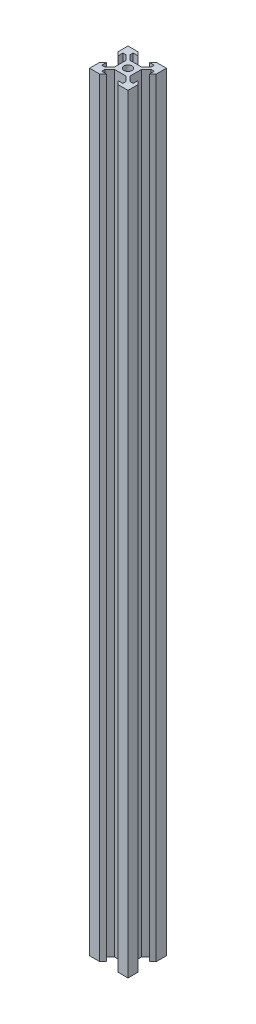
SolidWorks part; units mm, degrees
ref_plane "Front Plane" through (0, 0, 0) normal (0, 0, 1) x (1, 0, 0)
ref_plane "Top Plane" through (0, 0, 0) normal (0, 1, 0) x (1, 0, 0)
ref_plane "Right Plane" through (0, 0, 0) normal (1, 0, 0) x (0, 0, -1)
other "80mm"
sketch "Sketch1" plane through (0, 0, 0) normal (0, 1, 0) x (1, 0, 0)
  line L0 (-4.6984, 10) -> (-3, 8.2)
  line L1 (-10, 10) -> (-4.6984, 10)
  line L2 (-10, 10) -> (-10, 4.9076)
  line L3 (-10, -10) -> (-4.9076, -10)
  line L4 (10, 10) -> (10, 4.6984)
  line L5 (-10, 10) -> (10, -10) construction
  line L6 (-10, -10) -> (10, 10) construction
  line L7 (-3, 8.2) -> (-5.4993, 8.2)
  line L8 (-5.4993, 6.56) -> (-3, 4.0607)
  line L9 (-3, 4.0607) -> (3, 4.0607)
  line L10 (3, 4.0607) -> (5.4993, 6.56)
  line L11 (5.4993, 8.2) -> (3, 8.2)
  line L12 (3, 8.2) -> (4.9076, 10)
  line L13 (4.0607, 3) -> (4.0607, -3)
  line L14 (6.56, 5.4993) -> (4.0607, 3)
  line L15 (8.2, 3) -> (8.2, 5.4993)
  line L16 (10, 4.6984) -> (8.2, 3)
  line L17 (8.2, -3) -> (10, -4.9076)
  line L18 (8.2, -5.4993) -> (8.2, -3)
  line L19 (4.0607, -3) -> (6.56, -5.4993)
  line L20 (3, -4.0607) -> (-3, -4.0607)
  line L21 (5.4993, -6.56) -> (3, -4.0607)
  line L22 (3, -8.2) -> (5.4993, -8.2)
  line L23 (4.6984, -10) -> (3, -8.2)
  line L24 (-3, -8.2) -> (-4.9076, -10)
  line L25 (-5.4993, -8.2) -> (-3, -8.2)
  line L26 (-3, -4.0607) -> (-5.4993, -6.56)
  line L27 (-4.0607, -3) -> (-4.0607, 3)
  line L28 (-6.56, -5.4993) -> (-4.0607, -3)
  line L29 (-8.2, -3) -> (-8.2, -5.4993)
  line L30 (-10, -4.6984) -> (-8.2, -3)
  line L31 (-8.2, 3) -> (-10, 4.9076)
  line L32 (-8.2, 5.4993) -> (-8.2, 3)
  line L33 (-4.0607, 3) -> (-6.56, 5.4993)
  line L34 (-10, -4.6984) -> (-10, -10)
  line L35 (10, -4.9076) -> (10, -10)
  line L36 (4.9076, 10) -> (10, 10)
  line L37 (4.6984, -10) -> (10, -10)
  line L38 (-5.4993, 8.2) -> (-5.4993, 6.56)
  line L39 (8.2, 5.4993) -> (6.56, 5.4993)
  line L40 (5.4993, -8.2) -> (5.4993, -6.56)
  line L41 (-8.2, -5.4993) -> (-6.56, -5.4993)
  line L42 (5.4993, 6.56) -> (5.4993, 8.2)
  line L43 (6.56, -5.4993) -> (8.2, -5.4993)
  line L44 (-5.4993, -6.56) -> (-5.4993, -8.2)
  line L45 (-6.56, 5.4993) -> (-8.2, 5.4993)
  circle A0 centre (0, 0) radius 2.1
  point P0 (0, 0)
  point P42 (0, 0)
  dimension "D9" = 4.2
  dimension "D1" = 20
  dimension "D2" = 20
  dimension "D3" = 90
  dimension "D4" = 6
  dimension "D5" = 1.64
  dimension "D6" = 1.8
  dimension "D7" = 1.5
  dimension "D8" = 4
extrude "Ressalto-extrusão1" add sketch "Sketch1" along normal blind 400 contours L23 L37 L35 L17 L18 L19 L13 L14 L15 L16 L4 L36 L12 L11 L10 L9 L8 L7 L0 L1 L2 L31 L32 L33 L27 L28 L29 L30 L34 L3 L24 L25 L26 L20 L21 L22 A0 region at (-4.0549, 0, -8.9059)
